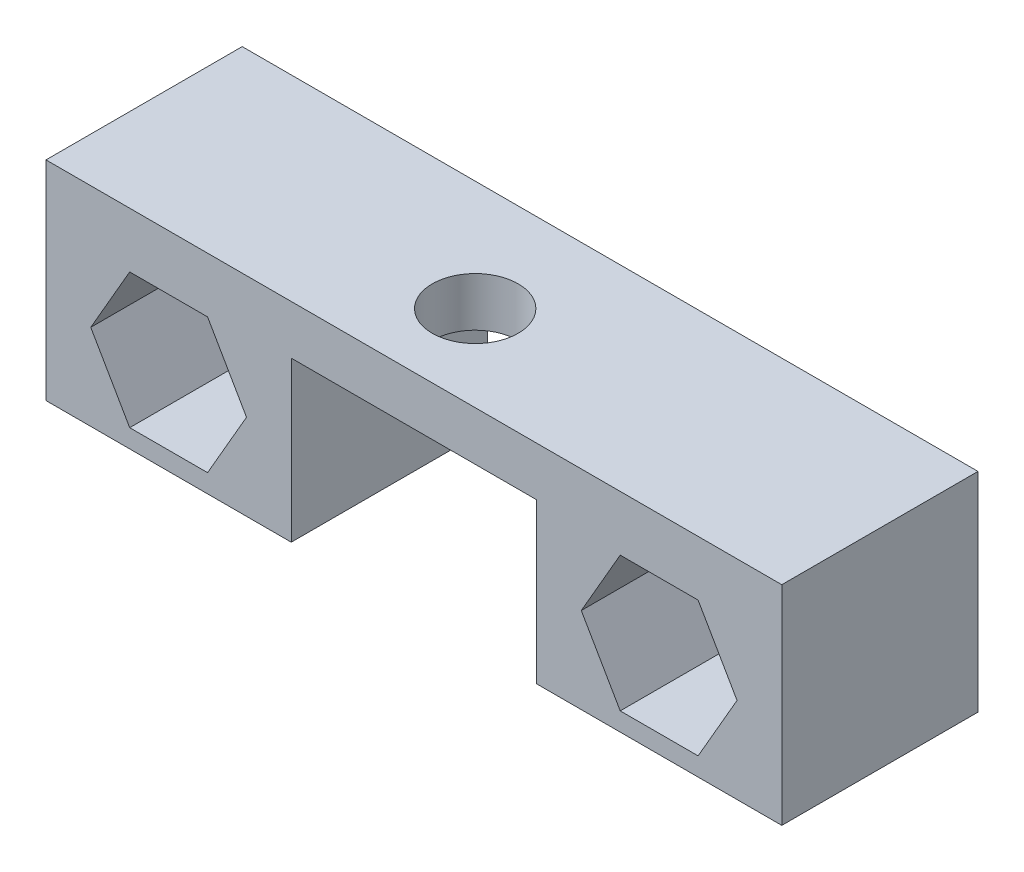
SolidWorks part; units mm, degrees
ref_plane "Front Plane" through (0, 0, 0) normal (0, 0, 1) x (1, 0, 0)
ref_plane "Top Plane" through (0, 0, 0) normal (0, 1, 0) x (1, 0, 0)
ref_plane "Right Plane" through (0, 0, 0) normal (1, 0, 0) x (0, 0, -1)
sketch "Sketch1" plane through (0, 0, 0) normal (0, 1, 0) x (1, 0, 0)
  line L0 (-1, -0.5) -> (-1, -4) construction
  line L5 (-15, 4) -> (15, 4)
  line L6 (-15, 4) -> (-15, -4)
  line L7 (-15, -4) -> (15, -4)
  line L8 (15, 4) -> (15, -4)
  line L9 (-15, 4) -> (15, -4) construction
  line L10 (-15, -4) -> (15, 4) construction
  line L11 (-1, 0) -> (0, 0) construction
  circle A0 centre (-1, -0.5) radius 1.75
  point P0 (0, 0)
  dimension "D3" = 3.5
  dimension "D1" = 30
  dimension "D2" = 8
  dimension "D4" = 3.5
  dimension "D5" = 1
extrude "Boss-Extrude1" add sketch "Sketch1" along normal blind 2
sketch "Sketch2" plane through (0, 0, 4) normal (0, 0, 1) x (1, 0, 0)
  line L0 (-10, -3) -> (10, -3) construction
  line L1 (-15, 0) -> (-5, 0)
  line L2 (-15, 0) -> (-15, -6.5)
  line L3 (-15, -6.5) -> (-5, -6.5)
  line L4 (-5, 0) -> (-5, -6.5)
  line L5 (15, 0) -> (5, 0)
  line L6 (15, 0) -> (15, -6.5)
  line L7 (15, -6.5) -> (5, -6.5)
  line L8 (5, 0) -> (5, -6.5)
  line L10 (-15, 2) -> (15, 2) construction
  line L11 (-15, 0) -> (15, 0) construction
  line L12 (-13.1754, -3) -> (-11.5877, -5.75)
  line L13 (-11.5877, -5.75) -> (-8.4123, -5.75)
  line L14 (-8.4123, -5.75) -> (-6.8246, -3)
  line L15 (-6.8246, -3) -> (-8.4123, -0.25)
  line L16 (-8.4123, -0.25) -> (-11.5877, -0.25)
  line L17 (-11.5877, -0.25) -> (-13.1754, -3)
  line L18 (8.4123, -0.25) -> (6.8246, -3)
  line L19 (6.8246, -3) -> (8.4123, -5.75)
  line L20 (8.4123, -5.75) -> (11.5877, -5.75)
  line L21 (11.5877, -5.75) -> (13.1754, -3)
  line L22 (13.1754, -3) -> (11.5877, -0.25)
  line L23 (11.5877, -0.25) -> (8.4123, -0.25)
  circle A2 centre (-10, -3) radius 2.75 construction
  circle A3 centre (10, -3) radius 2.75 construction
  point P10 (6.8246, -3.5)
  point P12 (-10, 0)
  point P13 (10, 0)
  point P17 (0, -3)
  point P22 (0, 0)
  dimension "D1" = 5.5
  dimension "D2" = 5.5
  dimension "D3" = 5
  dimension "D4" = 6.5
  dimension "D5" = 20
extrude "Boss-Extrude2" add sketch "Sketch2" against normal up to surface (8 mm away) up to face at (0, 1, -4)
sketch "Sketch3" plane through (0, 0, 0) normal (0, -1, 0) x (1, 0, 0)
  line L1 (-2.7321, -2.5) -> (0.7321, -2.5) construction
  line L2 (0.7321, -2.5) -> (2.4641, 0.5) construction
  line L3 (2.4641, 0.5) -> (0.7321, 3.5) construction
  line L4 (0.7321, 3.5) -> (-2.7321, 3.5) construction
  line L5 (-2.7321, 3.5) -> (-4.4641, 0.5) construction
  line L6 (-4.4641, 0.5) -> (-2.7321, -2.5) construction
  circle A0 centre (-1, 0.5) radius 3 construction
  dimension "D1" = 6
sketch "Sketch4" plane through (0, 0, -4) normal (0, 0, -1) x (-1, 0, 0)
  line L8 (-15, 2) -> (-15, -6.5)
  line L9 (-15, -6.5) -> (-5, -6.5)
  line L10 (-5, -6.5) -> (-5, 0)
  line L11 (-5, 0) -> (5, 0)
  line L12 (5, 0) -> (5, -6.5)
  line L13 (5, -6.5) -> (15, -6.5)
  line L14 (15, -6.5) -> (15, 2)
  line L15 (15, 2) -> (-15, 2)
  line L16 (-15, 2) -> (-15, -6.5)
  line L17 (-15, -6.5) -> (-5, -6.5)
  line L18 (-5, -6.5) -> (-5, 0)
  line L19 (-5, 0) -> (5, 0)
  line L20 (5, 0) -> (5, -6.5)
  line L21 (5, -6.5) -> (15, -6.5)
  line L22 (15, -6.5) -> (15, 2)
  line L23 (15, 2) -> (-15, 2)
  dimension "D1" = 0
extrude "Boss-Extrude3" add sketch "Sketch4" against normal offset from surface (2 mm away) 6 up to face at (0, -2.75, 4)
sketch "Sketch5" plane through (0, 0, -2) normal (0, 0, 1) x (1, 0, 0)
  line L0 (-10, -0.25) -> (-10, -5.75) construction
  line L1 (-8.4123, -0.25) -> (-11.5877, -0.25) construction
  line L2 (-11.5877, -5.75) -> (-8.4123, -5.75) construction
  line L3 (10, -0.25) -> (10, -5.75) construction
  line L4 (11.5877, -0.25) -> (8.4123, -0.25) construction
  line L5 (8.4123, -5.75) -> (11.5877, -5.75) construction
  line L6 (-11.5877, -5.75) -> (-8.4123, -5.75) construction
  circle A0 centre (-10, -3) radius 1.75
  circle A1 centre (10, -3) radius 1.75
  point P16 (-10, -6.25)
  dimension "D1" = 3.5
  dimension "D2" = 3.5
extrude "Cut-Extrude1" cut sketch "Sketch5" against normal through all
